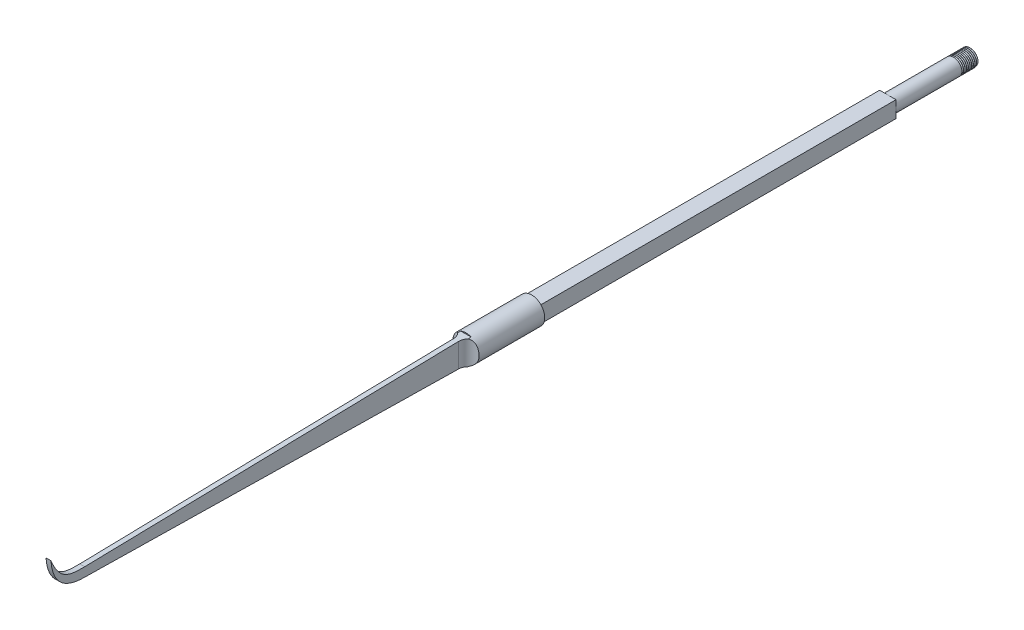
SolidWorks part; units mm, degrees
ref_plane "Front" through (0, 0, 0) normal (0, 0, 1) x (1, 0, 0)
ref_plane "Top" through (0, 0, 0) normal (0, 1, 0) x (1, 0, 0)
ref_plane "Right" through (0, 0, 0) normal (1, 0, 0) x (0, 0, -1)
sketch "Sketch1" plane through (0, 0, 0) normal (0, 0, 1) x (1, 0, 0)
  circle A0 centre (0, 0) radius 2.5
  dimension "D1" = 5
extrude "Boss-Extrude1" add sketch "Sketch1" along normal blind 25
sketch "Sketch2" plane through (0, 0, 25) normal (0, 0, 1) x (1, 0, 0)
  line L0 (0, 0) -> (4.001, 0) construction
  line L1 (-2.5, 2.5) -> (2.5, 2.5)
  line L2 (-2.5, 2.5) -> (-2.5, -2.5)
  line L3 (-2.5, -2.5) -> (2.5, -2.5)
  line L4 (2.5, 2.5) -> (2.5, -2.5)
  line L5 (0, 0) -> (0, 4.1573) construction
  point P8 (2.5, 0)
  point P9 (0, 2.5)
  dimension "D1" = 5
extrude "Boss-Extrude2" add sketch "Sketch2" along normal blind 108.5
sketch "Sketch3" plane through (0, 0, 133.5) normal (0, 0, 1) x (1, 0, 0)
  circle A0 centre (0, 0) radius 4
  dimension "D1" = 8
extrude "Boss-Extrude3" add sketch "Sketch3" along normal blind 20
ref_plane "Plane1" through (0, 0, 0) normal (1, 0, 0) x (0, 0, -1)
sketch "Sketch4" plane through (0, 0, 0) normal (1, 0, 0) x (0, 0, -1)
  line L2 (-138.5051, 4.0099) -> (-270.3902, 1.1144)
  line L3 (-138.5229, -3.9901) -> (-138.5051, 4.0099)
  line L7 (-138.5229, -3.9901) -> (-270.7526, -1.6372)
  spline S2 degree 3 poles (-270.3902, 1.1144) (-275.5657, 1.0008) (-278.0826, 1.6957) (-280.6655, 7.8495) knots 0 0 0 0 1 1 1 1
  spline S3 degree 3 poles (-270.7526, -1.6372) (-276.6275, -1.5315) (-280.2093, 1.4298) (-280.6655, 7.8495) knots 0 0 0 0 1 1 1 1
  dimension "D1" = 8
extrude "Boss-Extrude4" add sketch "Sketch4" along normal blind 0.75 and the other way blind 0.75
sketch "Sketch5" plane through (0, 0, 153.5) normal (0, 0, 1) x (1, 0, 0)
  circle A0 centre (0, 0) radius 4 construction
  circle A1 centre (0, 0) radius 4
  circle A2 centre (0, 0) radius 4.5
  dimension "D1" = 0.5
extrude "Cut-Extrude1" cut sketch "Sketch5" against normal blind 23.25
fillet "Fillet1" radius 3 2 edges at (0.75, -0.0214, 153.5) (-0.75, -0.0214, 153.5)
sketch "Sketch6" plane through (0, 0, 0) normal (0, 0, -1) x (-1, 0, 0)
  circle A0 centre (0, 0) radius 2.5 construction
  circle A1 centre (0, 0) radius 2.5
curve "Helix/Spiral1" pitch 0.5 height 5 radius 2.5 centre (0, 0, 0) axis (0, 0, 1) start towards (-1, 0, 0)
ref_plane "Plane2" through (-1.7678, -1.7678, 0) normal (0.7067, -0.7067, 0.0318) x (-0.7075, -0.706, 0.0318)
sketch "Sketch7" plane through (-1.7678, -1.7678, 0) normal (0.7067, -0.7067, 0.0318) x (-0.7075, -0.706, 0.0318)
  line L1 (-0.3905, -0.014) -> (0.0252, -0.254)
  line L2 (0.0252, -0.254) -> (0.0252, 0.226)
  line L3 (0.0252, 0.226) -> (-0.3905, -0.014)
  circle A0 centre (-0.1134, -0.014) radius 0.1386 construction
  point P1 (-0.1134, -0.014)
  dimension "D1" = 0.48
sweep "Cut-Sweep1" cut profiles "Sketch7" path "Helix/Spiral1" align with end faces yes
